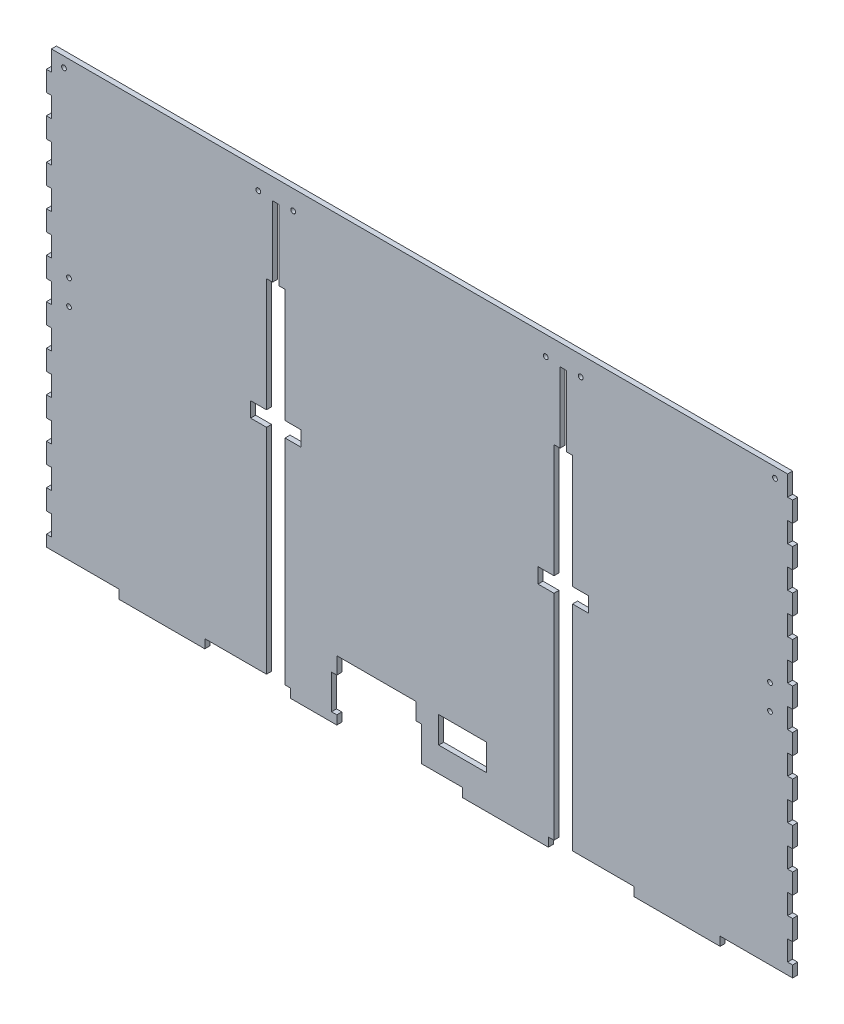
SolidWorks part; units mm, degrees
material "Acrylic (Medium-high impact)"
ref_plane "Front Plane" through (0, 0, 0) normal (0, 0, 1) x (1, 0, 0)
ref_plane "Top Plane" through (0, 0, 0) normal (0, 1, 0) x (1, 0, 0)
ref_plane "Right Plane" through (0, 0, 0) normal (1, 0, 0) x (0, 0, -1)
sketch "Sketch1" plane through (0, 0, 0) normal (0, 0, 1) x (1, 0, 0)
  line L0 (0, 139.7) -> (0, -139.7) construction
  line L1 (-406.4, 139.7) -> (406.4, 139.7)
  line L2 (-406.4, 139.7) -> (-406.4, -139.7)
  line L3 (-406.4, -139.7) -> (406.4, -139.7)
  line L4 (406.4, 139.7) -> (406.4, -139.7)
  line L49 (-381, 127) -> (-381, 114.3)
  line L54 (-381, 139.7) -> (-377.825, 139.7)
  line L55 (-381, 139.7) -> (-381, 127)
  line L56 (-381, 127) -> (-377.825, 127)
  line L57 (-377.825, 139.7) -> (-377.825, 127)
  line L58 (-381, 127) -> (-377.825, 127)
  line L59 (-377.825, 127) -> (-377.825, 114.3)
  line L60 (-381, 114.3) -> (-377.825, 114.3)
  line L61 (-381, 114.3) -> (-381, 101.6)
  line L62 (-381, 114.3) -> (-377.825, 114.3)
  line L63 (-377.825, 114.3) -> (-377.825, 101.6)
  line L64 (-381, 101.6) -> (-377.825, 101.6)
  line L65 (-381, 101.6) -> (-381, 88.9)
  line L66 (-381, 101.6) -> (-377.825, 101.6)
  line L67 (-377.825, 101.6) -> (-377.825, 88.9)
  line L68 (-381, 88.9) -> (-377.825, 88.9)
  line L69 (-381, 88.9) -> (-381, 76.2)
  line L70 (-381, 88.9) -> (-377.825, 88.9)
  line L71 (-377.825, 88.9) -> (-377.825, 76.2)
  line L72 (-381, 76.2) -> (-377.825, 76.2)
  line L73 (-381, 76.2) -> (-381, 63.5)
  line L74 (-381, 76.2) -> (-377.825, 76.2)
  line L75 (-377.825, 76.2) -> (-377.825, 63.5)
  line L76 (-381, 63.5) -> (-377.825, 63.5)
  line L77 (-381, 63.5) -> (-381, 50.8)
  line L78 (-381, 63.5) -> (-377.825, 63.5)
  line L79 (-377.825, 63.5) -> (-377.825, 50.8)
  line L80 (-381, 50.8) -> (-377.825, 50.8)
  line L81 (-381, 50.8) -> (-381, 38.1)
  line L82 (-381, 50.8) -> (-377.825, 50.8)
  line L83 (-377.825, 50.8) -> (-377.825, 38.1)
  line L84 (-381, 38.1) -> (-377.825, 38.1)
  line L85 (-381, 38.1) -> (-381, 25.4)
  line L86 (-381, 38.1) -> (-377.825, 38.1)
  line L87 (-377.825, 38.1) -> (-377.825, 25.4)
  line L88 (-381, 25.4) -> (-377.825, 25.4)
  line L89 (377.825, 127) -> (377.825, 114.3)
  line L90 (377.825, 139.7) -> (381, 139.7)
  line L91 (377.825, 139.7) -> (377.825, 127)
  line L92 (377.825, 127) -> (381, 127)
  line L93 (381, 139.7) -> (381, 127)
  line L94 (377.825, 127) -> (381, 127)
  line L95 (381, 127) -> (381, 114.3)
  line L96 (377.825, 114.3) -> (381, 114.3)
  line L97 (377.825, 114.3) -> (377.825, 101.6)
  line L98 (377.825, 114.3) -> (381, 114.3)
  line L99 (381, 114.3) -> (381, 101.6)
  line L100 (377.825, 101.6) -> (381, 101.6)
  line L101 (377.825, 101.6) -> (377.825, 88.9)
  line L102 (377.825, 101.6) -> (381, 101.6)
  line L103 (381, 101.6) -> (381, 88.9)
  line L104 (377.825, 88.9) -> (381, 88.9)
  line L105 (377.825, 88.9) -> (377.825, 76.2)
  line L106 (377.825, 88.9) -> (381, 88.9)
  line L107 (381, 88.9) -> (381, 76.2)
  line L108 (377.825, 76.2) -> (381, 76.2)
  line L109 (377.825, 76.2) -> (377.825, 63.5)
  line L110 (377.825, 76.2) -> (381, 76.2)
  line L111 (381, 76.2) -> (381, 63.5)
  line L112 (377.825, 63.5) -> (381, 63.5)
  line L113 (377.825, 63.5) -> (377.825, 50.8)
  line L114 (377.825, 63.5) -> (381, 63.5)
  line L115 (381, 63.5) -> (381, 50.8)
  line L116 (377.825, 50.8) -> (381, 50.8)
  line L117 (377.825, 50.8) -> (377.825, 38.1)
  line L118 (377.825, 50.8) -> (381, 50.8)
  line L119 (381, 50.8) -> (381, 38.1)
  line L120 (377.825, 38.1) -> (381, 38.1)
  line L121 (377.825, 38.1) -> (377.825, 25.4)
  line L122 (377.825, 38.1) -> (381, 38.1)
  line L123 (381, 38.1) -> (381, 25.4)
  line L124 (377.825, 25.4) -> (381, 25.4)
  line L125 (-352.2133, -134.112) -> (-352.2133, -139.7)
  line L126 (-406.4, -134.112) -> (-352.2133, -134.112)
  line L127 (-406.4, -134.112) -> (-406.4, -139.7)
  line L128 (-406.4, -139.7) -> (-352.2133, -139.7)
  line L129 (-352.2133, -134.112) -> (-352.2133, -139.7)
  line L130 (-352.2133, -134.112) -> (-298.0267, -134.112)
  line L131 (-298.0267, -134.112) -> (-298.0267, -139.7)
  line L132 (-352.2133, -139.7) -> (-298.0267, -139.7)
  line L133 (-298.0267, -134.112) -> (-298.0267, -139.7)
  line L134 (-298.0267, -134.112) -> (-243.84, -134.112)
  line L135 (-243.84, -134.112) -> (-243.84, -139.7)
  line L136 (-298.0267, -139.7) -> (-243.84, -139.7)
  line L137 (-243.84, -134.112) -> (-243.84, -139.7)
  line L138 (-243.84, -134.112) -> (-189.6533, -134.112)
  line L139 (-189.6533, -134.112) -> (-189.6533, -139.7)
  line L140 (-243.84, -139.7) -> (-189.6533, -139.7)
  line L141 (-189.6533, -134.112) -> (-189.6533, -139.7)
  line L142 (-189.6533, -134.112) -> (-135.4667, -134.112)
  line L143 (-135.4667, -134.112) -> (-135.4667, -139.7)
  line L144 (-189.6533, -139.7) -> (-135.4667, -139.7)
  line L145 (-135.4667, -134.112) -> (-135.4667, -139.7)
  line L146 (-135.4667, -134.112) -> (-81.28, -134.112)
  line L147 (-81.28, -134.112) -> (-81.28, -139.7)
  line L148 (-135.4667, -139.7) -> (-81.28, -139.7)
  line L149 (-81.28, -134.112) -> (-81.28, -139.7)
  line L150 (-81.28, -134.112) -> (-27.0933, -134.112)
  line L151 (-27.0933, -134.112) -> (-27.0933, -139.7)
  line L152 (-81.28, -139.7) -> (-27.0933, -139.7)
  line L153 (-27.0933, -134.112) -> (-27.0933, -139.7)
  line L154 (-27.0933, -134.112) -> (27.0933, -134.112)
  line L155 (27.0933, -134.112) -> (27.0933, -139.7)
  line L156 (-27.0933, -139.7) -> (27.0933, -139.7)
  line L157 (27.0933, -134.112) -> (27.0933, -139.7)
  line L158 (27.0933, -134.112) -> (81.28, -134.112)
  line L159 (81.28, -134.112) -> (81.28, -139.7)
  line L160 (27.0933, -139.7) -> (81.28, -139.7)
  line L161 (81.28, -134.112) -> (81.28, -139.7)
  line L162 (81.28, -134.112) -> (135.4667, -134.112)
  line L163 (135.4667, -134.112) -> (135.4667, -139.7)
  line L164 (81.28, -139.7) -> (135.4667, -139.7)
  line L165 (135.4667, -134.112) -> (135.4667, -139.7)
  line L166 (135.4667, -134.112) -> (189.6533, -134.112)
  line L167 (189.6533, -134.112) -> (189.6533, -139.7)
  line L168 (135.4667, -139.7) -> (189.6533, -139.7)
  line L169 (189.6533, -134.112) -> (189.6533, -139.7)
  line L170 (189.6533, -134.112) -> (243.84, -134.112)
  line L171 (243.84, -134.112) -> (243.84, -139.7)
  line L172 (189.6533, -139.7) -> (243.84, -139.7)
  line L173 (243.84, -134.112) -> (243.84, -139.7)
  line L174 (243.84, -134.112) -> (298.0267, -134.112)
  line L175 (298.0267, -134.112) -> (298.0267, -139.7)
  line L176 (243.84, -139.7) -> (298.0267, -139.7)
  line L177 (298.0267, -134.112) -> (298.0267, -139.7)
  line L178 (298.0267, -134.112) -> (352.2133, -134.112)
  line L179 (352.2133, -134.112) -> (352.2133, -139.7)
  line L180 (298.0267, -139.7) -> (352.2133, -139.7)
  line L181 (352.2133, -134.112) -> (352.2133, -139.7)
  line L182 (352.2133, -134.112) -> (406.4, -134.112)
  line L183 (406.4, -134.112) -> (406.4, -139.7)
  line L184 (352.2133, -139.7) -> (406.4, -139.7)
  line L205 (-90.678, 84.5227) -> (-90.678, -139.7) construction
  line L206 (90.678, 84.5227) -> (90.678, -139.7) construction
  line L207 (-90.678, -27.5886) -> (90.678, -27.5886) construction
  line L208 (-381, 25.4) -> (-381, 12.7)
  line L209 (-381, 25.4) -> (-377.825, 25.4)
  line L210 (-377.825, 25.4) -> (-377.825, 12.7)
  line L211 (-381, 12.7) -> (-377.825, 12.7)
  line L212 (-381, 12.7) -> (-381, 0)
  line L213 (-381, 12.7) -> (-377.825, 12.7)
  line L214 (-377.825, 12.7) -> (-377.825, 0)
  line L215 (-381, 0) -> (-377.825, 0)
  line L224 (-377.825, 0) -> (377.825, 0) construction
  line L229 (377.825, 25.4) -> (377.825, 12.7)
  line L230 (377.825, 25.4) -> (381, 25.4)
  line L231 (381, 25.4) -> (381, 12.7)
  line L232 (377.825, 12.7) -> (381, 12.7)
  line L233 (377.825, 12.7) -> (377.825, 0)
  line L234 (377.825, 12.7) -> (381, 12.7)
  line L235 (381, 12.7) -> (381, 0)
  line L236 (377.825, 0) -> (381, 0)
  line L237 (-381, 0) -> (-381, -12.7)
  line L238 (-381, 0) -> (-377.825, 0)
  line L239 (-377.825, 0) -> (-377.825, -12.7)
  line L240 (-381, -12.7) -> (-377.825, -12.7)
  line L241 (-381, -12.7) -> (-381, -25.4)
  line L242 (-381, -12.7) -> (-377.825, -12.7)
  line L243 (-377.825, -12.7) -> (-377.825, -25.4)
  line L244 (-381, -25.4) -> (-377.825, -25.4)
  line L245 (-381, -25.4) -> (-381, -38.1)
  line L246 (-381, -25.4) -> (-377.825, -25.4)
  line L247 (-377.825, -25.4) -> (-377.825, -38.1)
  line L248 (-381, -38.1) -> (-377.825, -38.1)
  line L249 (-381, -38.1) -> (-381, -50.8)
  line L250 (-381, -38.1) -> (-377.825, -38.1)
  line L251 (-377.825, -38.1) -> (-377.825, -50.8)
  line L252 (-381, -50.8) -> (-377.825, -50.8)
  line L253 (-381, -50.8) -> (-381, -63.5)
  line L254 (-381, -50.8) -> (-377.825, -50.8)
  line L255 (-377.825, -50.8) -> (-377.825, -63.5)
  line L256 (-381, -63.5) -> (-377.825, -63.5)
  line L257 (-381, -63.5) -> (-381, -76.2)
  line L258 (-381, -63.5) -> (-377.825, -63.5)
  line L259 (-377.825, -63.5) -> (-377.825, -76.2)
  line L260 (-381, -76.2) -> (-377.825, -76.2)
  line L261 (-381, -76.2) -> (-381, -88.9)
  line L262 (-381, -76.2) -> (-377.825, -76.2)
  line L263 (-377.825, -76.2) -> (-377.825, -88.9)
  line L264 (-381, -88.9) -> (-377.825, -88.9)
  line L265 (-381, -88.9) -> (-381, -101.6)
  line L266 (-381, -88.9) -> (-377.825, -88.9)
  line L267 (-377.825, -88.9) -> (-377.825, -101.6)
  line L268 (-381, -101.6) -> (-377.825, -101.6)
  line L269 (-381, -101.6) -> (-381, -114.3)
  line L270 (-381, -101.6) -> (-377.825, -101.6)
  line L271 (-377.825, -101.6) -> (-377.825, -114.3)
  line L272 (-381, -114.3) -> (-377.825, -114.3)
  line L273 (-381, -114.3) -> (-381, -127)
  line L274 (-381, -114.3) -> (-377.825, -114.3)
  line L275 (-377.825, -114.3) -> (-377.825, -127)
  line L276 (-381, -127) -> (-377.825, -127)
  line L277 (-381, -127) -> (-381, -139.7)
  line L278 (-381, -127) -> (-377.825, -127)
  line L279 (-377.825, -127) -> (-377.825, -139.7)
  line L280 (-381, -139.7) -> (-377.825, -139.7)
  line L281 (377.825, 0) -> (377.825, -12.7)
  line L282 (377.825, 0) -> (381, 0)
  line L283 (381, 0) -> (381, -12.7)
  line L284 (377.825, -12.7) -> (381, -12.7)
  line L285 (377.825, -12.7) -> (377.825, -25.4)
  line L286 (377.825, -12.7) -> (381, -12.7)
  line L287 (381, -12.7) -> (381, -25.4)
  line L288 (377.825, -25.4) -> (381, -25.4)
  line L289 (377.825, -25.4) -> (377.825, -38.1)
  line L290 (377.825, -25.4) -> (381, -25.4)
  line L291 (381, -25.4) -> (381, -38.1)
  line L292 (377.825, -38.1) -> (381, -38.1)
  line L293 (377.825, -38.1) -> (377.825, -50.8)
  line L294 (377.825, -38.1) -> (381, -38.1)
  line L295 (381, -38.1) -> (381, -50.8)
  line L296 (377.825, -50.8) -> (381, -50.8)
  line L297 (377.825, -50.8) -> (377.825, -63.5)
  line L298 (377.825, -50.8) -> (381, -50.8)
  line L299 (381, -50.8) -> (381, -63.5)
  line L300 (377.825, -63.5) -> (381, -63.5)
  line L301 (377.825, -63.5) -> (377.825, -76.2)
  line L302 (377.825, -63.5) -> (381, -63.5)
  line L303 (381, -63.5) -> (381, -76.2)
  line L304 (377.825, -76.2) -> (381, -76.2)
  line L305 (377.825, -76.2) -> (377.825, -88.9)
  line L306 (377.825, -76.2) -> (381, -76.2)
  line L307 (381, -76.2) -> (381, -88.9)
  line L308 (377.825, -88.9) -> (381, -88.9)
  line L309 (377.825, -88.9) -> (377.825, -101.6)
  line L310 (377.825, -88.9) -> (381, -88.9)
  line L311 (381, -88.9) -> (381, -101.6)
  line L312 (377.825, -101.6) -> (381, -101.6)
  line L313 (377.825, -101.6) -> (377.825, -114.3)
  line L314 (377.825, -101.6) -> (381, -101.6)
  line L315 (381, -101.6) -> (381, -114.3)
  line L316 (377.825, -114.3) -> (381, -114.3)
  line L317 (377.825, -114.3) -> (377.825, -127)
  line L318 (377.825, -114.3) -> (381, -114.3)
  line L319 (381, -114.3) -> (381, -127)
  line L320 (377.825, -127) -> (381, -127)
  line L321 (377.825, -127) -> (377.825, -139.7)
  line L322 (377.825, -127) -> (381, -127)
  line L323 (381, -127) -> (381, -139.7)
  line L324 (377.825, -139.7) -> (381, -139.7)
  point P6 (0, 0)
  point P128 (0, -27.5886)
  point P153 (0, 0)
  dimension "D4" = 12.7
  dimension "D5" = 3.175
  dimension "D10" = 181.356
  dimension "D12" = 755.65
  dimension "D8" = 812.8
  dimension "D11" = 54.1867
  dimension "D2" = 273.812
  dimension "D9" = 279.4
  dimension "D3" = 22
  dimension "D7" = 15
  dimension "D6" = 22
extrude "Main Extrude" add sketch "Sketch1" along normal blind 3.175 contours L321 L317 L313 L309 L305 L301 L297 L293 L289 L285 L281 L233 L229 L121 L117 L113 L109 L105 L101 L97 L89 L91 L1 L57 L59 L63 L67 L71 L75 L79 L83 L87 L210 L214 L239 L243 L247 L251 L255 L259 L263 L267 L271 L275 L279 L126 L130 L134 L138 L142 L146 | L277 L273 L269 L265 L261 L257 L253 L249 L245 L241 L237 L212 L208 L85 L81 L77 L73 L69 L65 L61 L49 L55 L1 L2 L126 | L319 L323 L182 L4 L1 L93 L95 L99 L103 L107 L111 L115 L119 L123 L231 L235 L283 L287 L291 L295 L299 L303 L307 L311 L315 | L126 L279 L3 L125 | L135 L134 L131 L3 | L143 L142 L139 L3 | L151 L150 L147 L3 | L159 L158 L155 L3 | L167 L166 L163 L3 | L175 L174 L171 L3 | L323 L182 L321 L184 | L89 L96 L95 L92 | L101 L104 L103 L100 | L109 L112 L111 L108 | L117 L120 L119 L116 | L229 L232 L231 L124 | L281 L284 L283 L236 | L289 L292 L291 L288 | L297 L300 L299 L296 | L305 L308 L307 L304 | L313 L316 L315 L312 | L323 L320 L321 L182 | L49 L60 L59 L56 | L65 L68 L67 L64 | L73 L76 L75 L72 | L81 L84 L83 L80 | L208 L211 L210 L88 | L237 L240 L239 L215 | L245 L248 L247 L244 | L253 L256 L255 L252 | L261 L264 L263 L260 | L269 L272 L271 L268 | L279 L276 L277 L126 | L277 L126 L2 L3 | L321 L182 L179 L3 | L182 L323 L3 L4 | L279 L126 L277 L128 region at (-393.7, 2.794, 0) region at (-393.7, -136.906, 0) region at (0, 2.794, 0) region at (-379.4125, 120.65, 0) region at (-379.4125, -130.556, 0) region at (-379.4125, -136.906, 0) region at (-365.0192, -136.906, 0) region at (393.7, 2.794, 0) region at (379.4125, 120.65, 0) region at (-379.4125, 95.25, 0) region at (-379.4125, -107.95, 0) region at (-270.9333, -136.906, 0) region at (393.7, -136.906, 0) region at (379.4125, 95.25, 0) region at (-379.4125, 69.85, 0) region at (-379.4125, -82.55, 0) region at (379.4125, -136.906, 0) region at (379.4125, -130.556, 0) region at (-162.56, -136.906, 0) region at (365.0192, -136.906, 0) region at (379.4125, 69.85, 0) region at (-379.4125, 44.45, 0) region at (-379.4125, -57.15, 0) region at (379.4125, -107.95, 0) region at (-54.1867, -136.906, 0) region at (270.9333, -136.906, 0) region at (379.4125, 44.45, 0) region at (-379.4125, 19.05, 0) region at (-379.4125, -31.75, 0) region at (379.4125, -82.55, 0) region at (54.1867, -136.906, 0) region at (162.56, -136.906, 0) region at (379.4125, 19.05, 0) region at (-379.4125, -6.35, 0) region at (379.4125, -57.15, 0) region at (379.4125, -6.35, 0) region at (379.4125, -31.75, 0)
sketch "Sketch8" plane through (0, 0, 3.175) normal (0, 0, 1) x (1, 0, 0)
  line L0 (-406.4, 139.7) -> (-406.4, -139.7) construction
  line L1 (-381, 28.2575) -> (-384.175, 28.2575)
  line L2 (-381, 28.2575) -> (-381, -3.6195)
  line L3 (-381, -3.6195) -> (-384.175, -3.6195)
  line L4 (-384.175, 28.2575) -> (-384.175, -3.6195)
  line L5 (-406.4, -139.7) -> (-352.2133, -139.7) construction
  line L6 (381, 28.2575) -> (384.175, 28.2575)
  line L7 (381, 28.2575) -> (381, -3.6195)
  line L8 (381, -3.6195) -> (384.175, -3.6195)
  line L9 (384.175, 28.2575) -> (384.175, -3.6195)
  line L11 (-381, 88.9) -> (-381, 76.2) construction
  line L12 (-352.2133, -134.112) -> (-298.0267, -134.112) construction
  line L13 (381, 88.9) -> (381, 76.2) construction
  line L14 (-393.7, -120.65) -> (393.7, -120.65) construction
  circle A0 centre (-393.7, -120.65) radius 1.5
  circle A1 centre (393.7, -120.65) radius 1.5
  point P6 (0, -120.65)
  point P16 (-384.175, 12.319)
  dimension "D5" = 3
  dimension "D1" = 31.877
  dimension "D2" = 3.175
  dimension "D3" = 146.431
  dimension "D4" = 19.05
  dimension "D6" = 12.7
extrude "Mount Holes" cut sketch "Sketch8" against normal through all
sketch "Sketch3" plane through (0, 0, 3.175) normal (0, 0, 1) x (1, 0, 0)
  line L0 (-135.4667, -134.112) -> (-81.28, -134.112) construction
  line L1 (-96.52, 126.492) -> (-84.836, 126.492)
  line L2 (-96.52, 126.492) -> (-96.52, -134.112)
  line L3 (-96.52, -134.112) -> (-84.836, -134.112)
  line L4 (-84.836, 126.492) -> (-84.836, -134.112)
  line L5 (81.28, -134.112) -> (135.4667, -134.112) construction
  line L6 (84.836, 126.492) -> (96.52, 126.492)
  line L7 (84.836, 126.492) -> (84.836, -134.112)
  line L8 (84.836, -134.112) -> (96.52, -134.112)
  line L9 (96.52, 126.492) -> (96.52, -134.112)
  line L10 (-84.836, -3.81) -> (84.836, -3.81) construction
  line L12 (-106.553, 10.3505) -> (-74.803, 10.3505)
  line L13 (-106.553, 10.3505) -> (-106.553, 0.8255)
  line L14 (-106.553, 0.8255) -> (-74.803, 0.8255)
  line L15 (-74.803, 10.3505) -> (-74.803, 0.8255)
  line L16 (74.803, 10.3505) -> (106.553, 10.3505)
  line L17 (74.803, 10.3505) -> (74.803, 0.8255)
  line L18 (74.803, 0.8255) -> (106.553, 0.8255)
  line L19 (106.553, 10.3505) -> (106.553, 0.8255)
  line L20 (-96.52, 126.492) -> (-92.6465, 126.492)
  line L21 (-96.52, 126.492) -> (-96.52, 82.042)
  line L22 (-96.52, 82.042) -> (-92.6465, 82.042)
  line L23 (-92.6465, 126.492) -> (-92.6465, 82.042)
  line L24 (-84.836, 126.492) -> (-88.7095, 126.492)
  line L25 (-84.836, 126.492) -> (-84.836, 82.042)
  line L26 (-84.836, 82.042) -> (-88.7095, 82.042)
  line L27 (-88.7095, 126.492) -> (-88.7095, 82.042)
  line L28 (84.836, 126.492) -> (88.7095, 126.492)
  line L29 (84.836, 126.492) -> (84.836, 82.042)
  line L30 (84.836, 82.042) -> (88.7095, 82.042)
  line L31 (88.7095, 126.492) -> (88.7095, 82.042)
  line L32 (96.52, 126.492) -> (92.6465, 126.492)
  line L33 (96.52, 126.492) -> (96.52, 82.042)
  line L34 (96.52, 82.042) -> (92.6465, 82.042)
  line L35 (92.6465, 126.492) -> (92.6465, 82.042)
  point P14 (-90.678, 126.492)
  point P15 (90.678, 126.492)
  point P16 (0, -3.81)
  point P27 (-90.678, 10.3505)
  point P28 (90.678, 10.3505)
  point P29 (-74.803, 5.588)
  dimension "D1" = 11.684
  dimension "D2" = 260.604
  dimension "D3" = 181.356
  dimension "D4" = 9.525
  dimension "D5" = 139.7
  dimension "D6" = 31.75
  dimension "D8" = 3.937
  dimension "D7" = 44.45
extrude "Door Slots" cut sketch "Sketch3" against normal through all contours L2 L12 L4 L1 | L2 L14 L4 L12 | L15 L12 L4 L14 | L13 L14 L2 L12 | L14 L2 L3 L4 | L7 L16 L9 L6 | L7 L18 L9 L16 | L19 L16 L9 L18 | L17 L18 L7 L16 | L18 L7 L8 L9 region at (-90.678, 56.2317, 3.175) region at (-90.678, 5.588, 3.175) region at (-101.5365, 5.588, 3.175) region at (-90.678, -66.6433, 3.175) region at (-79.8195, 5.588, 3.175) region at (90.678, 56.2317, 3.175) region at (90.678, 5.588, 3.175) region at (79.8195, 5.588, 3.175) region at (90.678, -66.6432, 3.175) region at (101.5365, 5.588, 3.175)
sketch "Sketch4" plane through (0, 0, 0) normal (0, 0, 1) x (1, 0, 0)
  line L1 (-81.28, -139.7) -> (-27.0933, -139.7) construction
  line L2 (-55.48, -112.41) -> (-52.178, -112.41)
  line L3 (-52.178, -112.41) -> (-52.178, -101.792)
  line L4 (-52.178, -101.792) -> (-2.178, -101.792)
  line L5 (-2.178, -101.792) -> (-2.178, -112.41)
  line L6 (-2.178, -112.41) -> (1.124, -112.41)
  line L9 (-55.48, -112.41) -> (-55.48, -134.112)
  line L10 (-55.48, -134.112) -> (-52.178, -134.112)
  line L11 (-52.178, -134.112) -> (-52.178, -139.7)
  line L12 (1.124, -112.41) -> (1.124, -134.112)
  line L13 (1.124, -134.112) -> (-2.178, -134.112)
  line L14 (-2.178, -134.112) -> (-2.178, -139.7)
  line L15 (-52.178, -139.7) -> (-2.178, -139.7)
  line L16 (-27.0933, -134.112) -> (27.0933, -134.112) construction
  line L18 (12.128, -101.792) -> (42.228, -101.792)
  line L19 (12.128, -101.792) -> (12.128, -118.491)
  line L20 (12.128, -118.491) -> (42.228, -118.491)
  line L21 (42.228, -101.792) -> (42.228, -118.491)
  line L22 (-27.0933, -134.112) -> (27.0933, -134.112) construction
  line L24 (-96.52, -134.112) -> (-84.836, -134.112) construction
  line L25 (84.836, -134.112) -> (96.52, -134.112) construction
  point P9 (-27.178, -101.792)
  point P10 (-27.178, -139.7)
  point P22 (27.178, -118.491)
  point P25 (90.678, -134.112)
  point P30 (-90.678, -134.112)
  dimension "D1" = 50
  dimension "D2" = 3.302
  dimension "D4" = 21.702
  dimension "D5" = 30.1
  dimension "D9" = 63.5
  dimension "D8" = 63.5
  dimension "D3" = 32.32
  dimension "D7" = 15.621
  dimension "D6" = 32.32
extrude "Trough and Lever Holes" cut sketch "Sketch4" along normal through all contours L11 L15 L14 L13 L12 L6 L5 L4 L3 L2 L9 L10 | L21 L18 L19 L20 region at (-27.178, -120.9228, 0) region at (27.178, -110.1415, 0)
sketch "Sketch5" plane through (0, 0, 3.175) normal (0, 0, 1) x (1, 0, 0)
  line L0 (-90.678, 126.492) -> (-90.678, -134.112) construction
  line L1 (-96.52, 126.492) -> (-84.836, 126.492) construction
  line L2 (-96.52, -134.112) -> (-84.836, -134.112) construction
  line L3 (90.678, 126.492) -> (90.678, -134.112) construction
  line L4 (84.836, 126.492) -> (96.52, 126.492) construction
  line L5 (84.836, -134.112) -> (96.52, -134.112) construction
  line L6 (-135.4667, -134.112) -> (-96.52, -134.112) construction
  line L19 (-99.998, -134.112) -> (-96.3199, -134.112)
  line L20 (-99.998, -134.112) -> (-99.998, -108.712)
  line L21 (-99.998, -108.712) -> (-96.3199, -108.712)
  line L22 (-96.3199, -134.112) -> (-96.3199, -108.712)
  line L24 (-99.998, -108.712) -> (-96.3199, -108.712)
  line L25 (-99.998, -108.712) -> (-99.998, -83.312)
  line L26 (-99.998, -83.312) -> (-96.3199, -83.312)
  line L27 (-96.3199, -108.712) -> (-96.3199, -83.312)
  line L28 (-96.3199, -83.312) -> (-99.998, -83.312)
  line L29 (-96.3199, -83.312) -> (-96.3199, -57.912)
  line L30 (-96.3199, -57.912) -> (-99.998, -57.912)
  line L31 (-99.998, -83.312) -> (-99.998, -57.912)
  line L32 (-99.998, -57.912) -> (-96.3199, -57.912)
  line L33 (-99.998, -57.912) -> (-99.998, -32.512)
  line L34 (-99.998, -32.512) -> (-96.3199, -32.512)
  line L35 (-96.3199, -57.912) -> (-96.3199, -32.512)
  line L36 (-96.3199, -32.512) -> (-99.998, -32.512)
  line L37 (-96.3199, -32.512) -> (-96.3199, -7.112)
  line L38 (-96.3199, -7.112) -> (-99.998, -7.112)
  line L39 (-99.998, -32.512) -> (-99.998, -7.112)
  line L40 (-81.358, -108.712) -> (-85.0361, -108.712)
  line L41 (-85.0361, -134.112) -> (-85.0361, -108.712)
  line L42 (-81.358, -134.112) -> (-85.0361, -134.112)
  line L43 (-81.358, -134.112) -> (-81.358, -108.712)
  line L44 (-81.358, -83.312) -> (-85.0361, -83.312)
  line L45 (-85.0361, -108.712) -> (-85.0361, -83.312)
  line L46 (-81.358, -108.712) -> (-85.0361, -108.712)
  line L47 (-81.358, -108.712) -> (-81.358, -83.312)
  line L48 (-85.0361, -57.912) -> (-81.358, -57.912)
  line L49 (-81.358, -83.312) -> (-81.358, -57.912)
  line L50 (-85.0361, -83.312) -> (-81.358, -83.312)
  line L51 (-85.0361, -83.312) -> (-85.0361, -57.912)
  line L52 (-81.358, -32.512) -> (-85.0361, -32.512)
  line L53 (-85.0361, -57.912) -> (-85.0361, -32.512)
  line L54 (-81.358, -57.912) -> (-85.0361, -57.912)
  line L55 (-81.358, -57.912) -> (-81.358, -32.512)
  line L56 (-85.0361, -7.112) -> (-81.358, -7.112)
  line L57 (-81.358, -32.512) -> (-81.358, -7.112)
  line L58 (-85.0361, -32.512) -> (-81.358, -32.512)
  line L59 (-85.0361, -32.512) -> (-85.0361, -7.112)
  line L60 (0, -1.7463) -> (0, 1.7463) construction
  line L61 (99.998, -108.712) -> (96.3199, -108.712)
  line L62 (96.3199, -134.112) -> (96.3199, -108.712)
  line L63 (99.998, -134.112) -> (96.3199, -134.112)
  line L64 (99.998, -134.112) -> (99.998, -108.712)
  line L65 (99.998, -83.312) -> (96.3199, -83.312)
  line L66 (96.3199, -108.712) -> (96.3199, -83.312)
  line L67 (99.998, -108.712) -> (96.3199, -108.712)
  line L68 (99.998, -108.712) -> (99.998, -83.312)
  line L69 (96.3199, -57.912) -> (99.998, -57.912)
  line L70 (99.998, -83.312) -> (99.998, -57.912)
  line L71 (96.3199, -83.312) -> (99.998, -83.312)
  line L72 (96.3199, -83.312) -> (96.3199, -57.912)
  line L73 (99.998, -32.512) -> (96.3199, -32.512)
  line L74 (96.3199, -57.912) -> (96.3199, -32.512)
  line L75 (99.998, -57.912) -> (96.3199, -57.912)
  line L76 (99.998, -57.912) -> (99.998, -32.512)
  line L77 (96.3199, -7.112) -> (99.998, -7.112)
  line L78 (99.998, -32.512) -> (99.998, -7.112)
  line L79 (96.3199, -32.512) -> (99.998, -32.512)
  line L80 (96.3199, -32.512) -> (96.3199, -7.112)
  line L81 (85.0361, -32.512) -> (85.0361, -7.112)
  line L82 (85.0361, -32.512) -> (81.358, -32.512)
  line L83 (81.358, -32.512) -> (81.358, -7.112)
  line L84 (85.0361, -7.112) -> (81.358, -7.112)
  line L85 (81.358, -57.912) -> (81.358, -32.512)
  line L86 (81.358, -57.912) -> (85.0361, -57.912)
  line L87 (85.0361, -57.912) -> (85.0361, -32.512)
  line L88 (81.358, -32.512) -> (85.0361, -32.512)
  line L89 (85.0361, -83.312) -> (85.0361, -57.912)
  line L90 (85.0361, -83.312) -> (81.358, -83.312)
  line L91 (81.358, -83.312) -> (81.358, -57.912)
  line L92 (85.0361, -57.912) -> (81.358, -57.912)
  line L93 (81.358, -108.712) -> (81.358, -83.312)
  line L94 (81.358, -108.712) -> (85.0361, -108.712)
  line L95 (85.0361, -108.712) -> (85.0361, -83.312)
  line L96 (81.358, -83.312) -> (85.0361, -83.312)
  line L97 (81.358, -134.112) -> (81.358, -108.712)
  line L98 (81.358, -134.112) -> (85.0361, -134.112)
  line L99 (85.0361, -134.112) -> (85.0361, -108.712)
  line L100 (81.358, -108.712) -> (85.0361, -108.712)
  dimension "D1" = 25.4
  dimension "D3" = 5.6419
  dimension "D2" = 9.32
extrude "Door Guide Slots" [suppressed] cut sketch "Sketch5" against normal through all contours L21 L27 L26 L25 | L30 L35 L34 L33 | L48 L55 L52 L53 | L40 L47 L44 L45 | L86 L87 L82 L85 | L94 L95 L90 L93 | L69 L76 L73 L74 | L61 L68 L65 L66
sketch "Sketch7" plane through (0, 0, 3.175) normal (0, 0, 1) x (1, 0, 0)
  line L0 (-25.908, -109.9715) -> (25.908, -109.9715) construction
  line L1 (-56.008, -105.601) -> (-25.908, -105.601)
  line L2 (-56.008, -105.601) -> (-56.008, -114.342)
  line L3 (-56.008, -114.342) -> (-25.908, -114.342)
  line L4 (-25.908, -105.601) -> (-25.908, -114.342)
  line L5 (56.008, -105.601) -> (25.908, -105.601)
  line L6 (56.008, -105.601) -> (56.008, -114.342)
  line L7 (56.008, -114.342) -> (25.908, -114.342)
  line L8 (25.908, -105.601) -> (25.908, -114.342)
  line L9 (0, -109.9715) -> (0, 0) construction
  line L10 (-135.4667, -134.112) -> (-96.52, -134.112) construction
  line L11 (1.124, -134.112) -> (27.0933, -134.112) construction
  dimension "D1" = 28.511
  dimension "D2" = 30.1
  dimension "D3" = 51.816
  dimension "D4" = 19.77
extrude "Lever Holes" [suppressed] cut sketch "Sketch7" against normal through all
sketch "Sketch10" plane through (0, 0, 3.175) normal (0, 0, 1) x (1, 0, 0)
  line L0 (-101.678, 127.492) -> (-79.678, 127.492) construction
  line L2 (-92.6465, 126.492) -> (-88.7095, 126.492) construction
  line L3 (-90.678, 127.492) -> (-90.678, 126.492) construction
  line L4 (79.678, 127.492) -> (101.678, 127.492) construction
  line L5 (90.678, 127.492) -> (90.678, 126.492) construction
  line L6 (88.7095, 126.492) -> (92.6465, 126.492) construction
  circle A0 centre (-101.678, 127.492) radius 1.5
  circle A1 centre (-79.678, 127.492) radius 1.5
  circle A2 centre (79.678, 127.492) radius 1.5
  circle A3 centre (101.678, 127.492) radius 1.5
  dimension "D1" = 3
  dimension "D2" = 22
  dimension "D3" = 1
extrude "Door Guide Mount Holes" cut sketch "Sketch10" against normal through all
sketch "Sketch12" plane through (0, 0, 3.175) normal (0, 0, 1) x (1, 0, 0)
  line L0 (-246.507, 20.193) -> (-246.507, 4.445) construction
  line L1 (-221.107, 20.193) -> (-221.107, 4.445) construction
  line L2 (-246.507, 20.193) -> (-221.107, 20.193) construction
  line L3 (-246.507, 4.445) -> (-221.107, 4.445) construction
  line L4 (-243.332, 133.35) -> (-224.282, 133.35) construction
  line L5 (-406.4, 139.7) -> (406.4, 139.7) construction
  line L6 (-233.807, 20.193) -> (-233.807, 133.35) construction
  line L7 (-243.84, -134.112) -> (-189.6533, -134.112) construction
  line L8 (0, -1.7463) -> (0, 1.7463) construction
  line L9 (233.807, 20.193) -> (233.807, 133.35) construction
  line L10 (243.332, 133.35) -> (224.282, 133.35) construction
  line L11 (246.507, 4.445) -> (221.107, 4.445) construction
  line L12 (246.507, 20.193) -> (221.107, 20.193) construction
  line L13 (221.107, 20.193) -> (221.107, 4.445) construction
  line L14 (246.507, 20.193) -> (246.507, 4.445) construction
  circle A0 centre (-246.507, 20.193) radius 1.5
  circle A1 centre (-246.507, 4.445) radius 1.5
  circle A2 centre (-221.107, 4.445) radius 1.5
  circle A3 centre (-221.107, 20.193) radius 1.5
  circle A4 centre (-243.332, 133.35) radius 1.5
  circle A5 centre (-224.282, 133.35) radius 1.5
  circle A6 centre (224.282, 133.35) radius 1.5
  circle A7 centre (243.332, 133.35) radius 1.5
  circle A8 centre (221.107, 20.193) radius 1.5
  circle A9 centre (221.107, 4.445) radius 1.5
  circle A10 centre (246.507, 4.445) radius 1.5
  circle A11 centre (246.507, 20.193) radius 1.5
  point P12 (-233.807, 133.35)
  dimension "D1" = 3
  dimension "D2" = 233.807
  dimension "D3" = 19.05
  dimension "D4" = 6.35
  dimension "D5" = 25.4
  dimension "D6" = 15.748
  dimension "D7" = 138.557
extrude "Extension Clip Holes" cut sketch "Sketch12" against normal through all
sketch "Sketch11" plane through (0, 0, 3.175) normal (0, 0, 1) x (1, 0, 0)
  line L0 (-232.2195, 139.7) -> (-232.2195, 127)
  line L1 (-232.2195, 127) -> (-235.3945, 127)
  line L2 (-235.3945, 127) -> (-235.3945, 114.3)
  line L3 (-235.3945, 114.3) -> (-232.2195, 114.3)
  line L4 (232.2195, 139.7) -> (232.2195, 127)
  line L5 (232.2195, 127) -> (235.3945, 127)
  line L6 (235.3945, 127) -> (235.3945, 114.3)
  line L7 (235.3945, 114.3) -> (232.2195, 114.3)
  line L9 (-381, 127) -> (-377.825, 127) construction
  line L10 (-377.825, 139.7) -> (-377.825, 127) construction
  line L11 (235.3945, 120.65) -> (-235.3945, 120.65) construction
  line L12 (-232.2195, 114.3) -> (-232.2195, 101.6)
  line L13 (-232.2195, 101.6) -> (-235.3945, 101.6)
  line L14 (-235.3945, 101.6) -> (-235.3945, 88.9)
  line L15 (-235.3945, 88.9) -> (-232.2195, 88.9)
  line L16 (232.2195, 114.3) -> (232.2195, 101.6)
  line L17 (232.2195, 101.6) -> (235.3945, 101.6)
  line L18 (235.3945, 101.6) -> (235.3945, 88.9)
  line L19 (235.3945, 88.9) -> (232.2195, 88.9)
  line L20 (-232.2195, 88.9) -> (-232.2195, 76.2)
  line L21 (-232.2195, 76.2) -> (-235.3945, 76.2)
  line L22 (-235.3945, 76.2) -> (-235.3945, 63.5)
  line L23 (-235.3945, 63.5) -> (-232.2195, 63.5)
  line L24 (232.2195, 88.9) -> (232.2195, 76.2)
  line L25 (232.2195, 76.2) -> (235.3945, 76.2)
  line L26 (235.3945, 76.2) -> (235.3945, 63.5)
  line L27 (235.3945, 63.5) -> (232.2195, 63.5)
  line L28 (-232.2195, 63.5) -> (-232.2195, 50.8)
  line L29 (-232.2195, 50.8) -> (-235.3945, 50.8)
  line L30 (-235.3945, 50.8) -> (-235.3945, 38.1)
  line L31 (-235.3945, 38.1) -> (-232.2195, 38.1)
  line L32 (232.2195, 63.5) -> (232.2195, 50.8)
  line L33 (232.2195, 50.8) -> (235.3945, 50.8)
  line L34 (235.3945, 50.8) -> (235.3945, 38.1)
  line L35 (235.3945, 38.1) -> (232.2195, 38.1)
  line L36 (-232.2195, 38.1) -> (-232.2195, 25.4)
  line L37 (-232.2195, 25.4) -> (-235.3945, 25.4)
  line L38 (-235.3945, 25.4) -> (-235.3945, 12.7)
  line L39 (-235.3945, 12.7) -> (-232.2195, 12.7)
  line L40 (232.2195, 38.1) -> (232.2195, 25.4)
  line L41 (232.2195, 25.4) -> (235.3945, 25.4)
  line L42 (235.3945, 25.4) -> (235.3945, 12.7)
  line L43 (235.3945, 12.7) -> (232.2195, 12.7)
  line L44 (-232.2195, 12.7) -> (-232.2195, 0)
  line L45 (-232.2195, 0) -> (-235.3945, 0)
  line L46 (-235.3945, 0) -> (-235.3945, -12.7)
  line L47 (-235.3945, -12.7) -> (-232.2195, -12.7)
  line L48 (232.2195, 12.7) -> (232.2195, 0)
  line L50 (232.2195, 0) -> (235.3945, 0)
  line L52 (235.3945, 0) -> (235.3945, -12.7)
  line L53 (235.3945, -12.7) -> (232.2195, -12.7)
  line L54 (-232.2195, -12.7) -> (-232.2195, -25.4)
  line L55 (-232.2195, -25.4) -> (-235.3945, -25.4)
  line L56 (-235.3945, -25.4) -> (-235.3945, -38.1)
  line L57 (-235.3945, -38.1) -> (-232.2195, -38.1)
  line L58 (232.2195, -12.7) -> (232.2195, -25.4)
  line L59 (232.2195, -25.4) -> (235.3945, -25.4)
  line L60 (235.3945, -25.4) -> (235.3945, -38.1)
  line L61 (235.3945, -38.1) -> (232.2195, -38.1)
  line L62 (-232.2195, -38.1) -> (-232.2195, -50.8)
  line L63 (-232.2195, -50.8) -> (-235.3945, -50.8)
  line L64 (-235.3945, -50.8) -> (-235.3945, -63.5)
  line L65 (-235.3945, -63.5) -> (-232.2195, -63.5)
  line L66 (232.2195, -38.1) -> (232.2195, -50.8)
  line L67 (232.2195, -50.8) -> (235.3945, -50.8)
  line L68 (235.3945, -50.8) -> (235.3945, -63.5)
  line L69 (235.3945, -63.5) -> (232.2195, -63.5)
  line L70 (-232.2195, -63.5) -> (-232.2195, -76.2)
  line L71 (-232.2195, -76.2) -> (-235.3945, -76.2)
  line L72 (-235.3945, -76.2) -> (-235.3945, -88.9)
  line L73 (-235.3945, -88.9) -> (-232.2195, -88.9)
  line L74 (232.2195, -63.5) -> (232.2195, -76.2)
  line L75 (232.2195, -76.2) -> (235.3945, -76.2)
  line L76 (235.3945, -76.2) -> (235.3945, -88.9)
  line L77 (235.3945, -88.9) -> (232.2195, -88.9)
  line L78 (-232.2195, -88.9) -> (-232.2195, -101.6)
  line L79 (-232.2195, -101.6) -> (-235.3945, -101.6)
  line L80 (-235.3945, -101.6) -> (-235.3945, -114.3)
  line L81 (-235.3945, -114.3) -> (-232.2195, -114.3)
  line L82 (232.2195, -88.9) -> (232.2195, -101.6)
  line L83 (232.2195, -101.6) -> (235.3945, -101.6)
  line L84 (235.3945, -101.6) -> (235.3945, -114.3)
  line L85 (235.3945, -114.3) -> (232.2195, -114.3)
  line L86 (-232.2195, -114.3) -> (-232.2195, -127)
  line L87 (-232.2195, -127) -> (-235.3945, -127)
  line L88 (-235.3945, -127) -> (-235.3945, -139.7)
  line L90 (232.2195, -114.3) -> (232.2195, -127)
  line L91 (232.2195, -127) -> (235.3945, -127)
  line L92 (235.3945, -127) -> (235.3945, -139.7)
  line L98 (-406.4, 139.7) -> (406.4, 139.7)
  line L99 (-406.4, 139.7) -> (-406.4, -139.7)
  line L100 (-406.4, -139.7) -> (406.4, -139.7)
  line L101 (406.4, 139.7) -> (406.4, -139.7)
  line L102 (-235.3945, -139.7) -> (-232.2195, -139.7)
  line L103 (235.3945, -139.7) -> (232.2195, -139.7)
  point P14 (-233.807, 127)
  point P15 (233.807, 114.3)
  point P18 (0, 120.65)
  dimension "D2" = 11
  dimension "D1" = 467.614
extrude "Extended Side Cut" [suppressed] cut sketch "Sketch11" against normal through all
extrude "Extension Center Cut" cut sketch "Sketch11<3>" against normal through all contours L99 L100 L39 L31 L23 L15 L2 L1 L98 | L101 L98 L80 L77 L76 L75 L72 L69 L68 L67 L64 L61 L60 L59 L56 L53 L52 L50 L100 region at (-320.0962, 0.0584, 3.175) region at (320.0962, 0.0584, 3.175)
sketch "Sketch11<3>" plane through (0, 0, 3.175) normal (0, 0, 1) x (1, 0, 0) same geometry as "Sketch11"
sketch "Sketch14" plane through (0, 0, 3.175) normal (0, 0, 1) x (1, 0, 0)
  line L1 (-232.2195, 139.7) -> (232.2195, 139.7)
  line L2 (-232.2195, 139.7) -> (-232.2195, 165.1)
  line L3 (-232.2195, 165.1) -> (232.2195, 165.1)
  line L4 (232.2195, 139.7) -> (232.2195, 165.1)
  dimension "D1" = 25.4
extrude "Extra Inch" [suppressed] add sketch "Sketch14" against normal up to surface (3.175 mm away)
sketch "Sketch15" [suppressed] plane through (0, 0, 3.175) normal (0, 0, 1) x (1, 0, 0)
  line L1 (-232.2195, 139.7) -> (232.2195, 139.7)
  line L2 (-232.2195, 139.7) -> (-232.2195, 165.1)
  line L3 (-232.2195, 165.1) -> (232.2195, 165.1)
  line L4 (232.2195, 139.7) -> (232.2195, 165.1)
  dimension "D1" = 25.4
extrude "Back Extra Inch" [suppressed] add sketch "Sketch15" against normal up to surface (3.175 mm away)
sketch "Sketch16" [suppressed] plane through (0, 0, 3.175) normal (0, 0, 1) x (1, 0, 0)
  line L1 (-232.2195, 139.7) -> (-406.4, 139.7)
  line L2 (-232.2195, 139.7) -> (-232.2195, 165.1)
  line L3 (-232.2195, 165.1) -> (-406.4, 165.1)
  line L4 (-406.4, 139.7) -> (-406.4, 165.1)
  dimension "D1" = 25.4
extrude "Extended Extra Inch" [suppressed] add sketch "Sketch16" against normal up to surface (3.175 mm away)
equation "\"bottomThickness\"= .220in"
equation "\"wallThickness\"= .125in"
equation "\"D4@Sketch1\"=\"D9@Sketch1\"/\"D3@Sketch1\""
equation "\"D5@Sketch1\"=\"wallThickness\""
equation "\"D1@Main Extrude\" = \"wallThickness\""
equation "\"D1@Sketch3\"=\"wallThickness\"*2+.19in+.02in"
equation "\"D2@Sketch4\"=\"wallThickness\"+.005in"
equation "\"D11@Sketch1\"=\"D8@Sketch1\"/\"D7@Sketch1\""
equation "\"D9@Sketch1\"=\"D2@Sketch1\"+\"bottomThickness\""
equation "\"D3@Sketch5\"=(\"wallThickness\"*2+.19in+.04)/2-(\"wallThickness\"-\"wallThickness\"/tan(80))*cos(80)"
equation "\"D8@Sketch3\"=\"wallThickness\"+.03in"
equation "\"D4@Sketch4\"=\"wallThickness\"+18.4mm+.005in"
equation "\"D2@Sketch5\"=(\"wallThickness\"*2+.19in+.04)/2+\"wallThickness\"/sin(80)"
